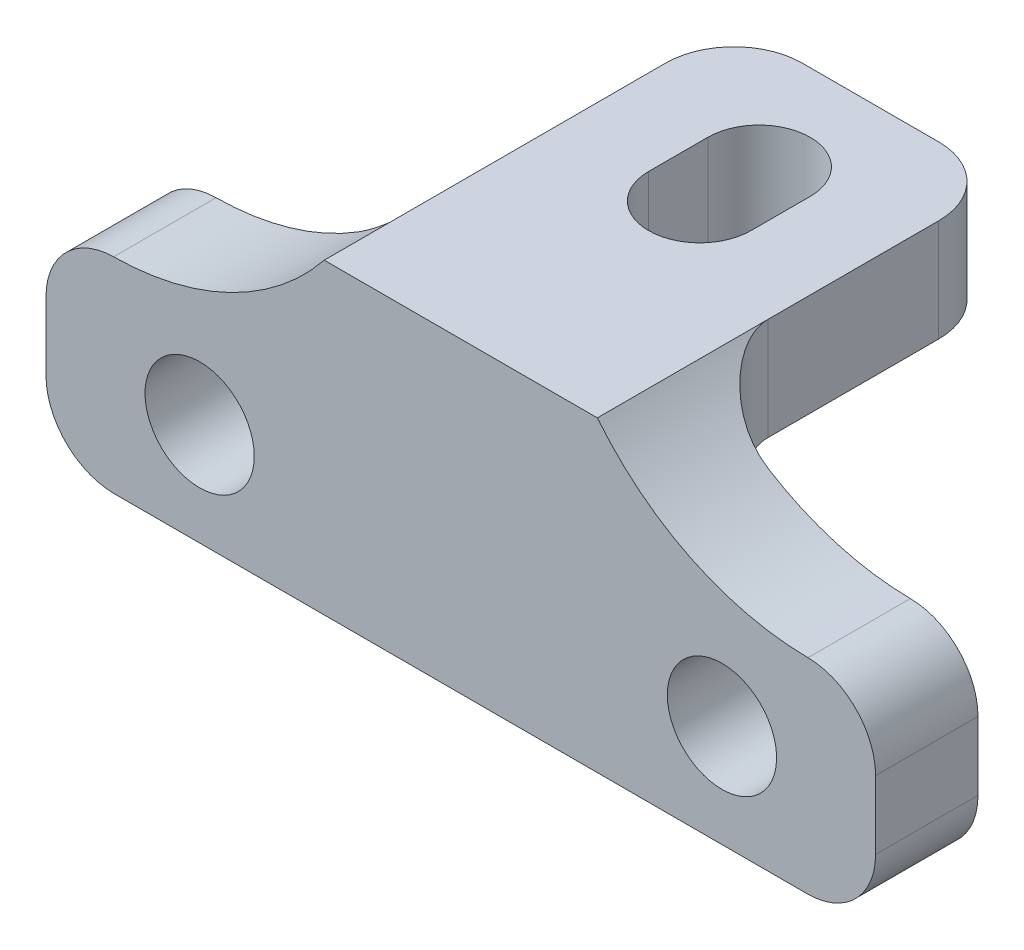
SolidWorks part; units mm, degrees
ref_plane "Plano frontal" through (0, 0, 0) normal (0, 0, 1) x (1, 0, 0)
ref_plane "Plano superior" through (0, 0, 0) normal (0, 1, 0) x (1, 0, 0)
ref_plane "Plano direito" through (0, 0, 0) normal (1, 0, 0) x (0, 0, -1)
sketch "Esboço1" plane through (0, 0, 0) normal (0, 0, 1) x (1, 0, 0)
  line L0 (-37.357, 24.6529) -> (-37.357, 18.6529) construction
  line L1 (-49.507, 24.6529) -> (-25.207, 24.6529)
  line L2 (-49.507, 24.6529) -> (-49.507, 18.6529)
  line L3 (-49.507, 18.6529) -> (-25.207, 18.6529)
  line L4 (-25.207, 24.6529) -> (-25.207, 18.6529)
  line L5 (-49.507, 21.6529) -> (-25.207, 21.6529) construction
  circle A0 centre (-45.007, 21.6529) radius 1.6
  circle A1 centre (-29.707, 21.6529) radius 1.6
  point P10 (0, 0)
  dimension "D3" = 15.3
  dimension "D1" = 24.3
  dimension "D2" = 6
base flange "Flange-base1" sketch "Esboço1" thickness 3 reverse thickness direction no parameters "D1"=0.7366
sketch "Esboço6" plane through (0, 24.6529, 0) normal (0, 1, 0) x (1, 0, 0)
  line L0 (-49.507, 0) -> (-25.207, 0) construction
  line L1 (-41.357, 0) -> (-33.357, 0)
  line L2 (-41.357, 0) -> (-41.357, 12)
  line L3 (-41.357, 12) -> (-33.357, 12)
  line L4 (-33.357, 0) -> (-33.357, 12)
  line L6 (-25.207, 0) -> (-49.507, 0) construction
  line L7 (-37.357, 3) -> (-37.357, 1.2859) construction
  line L8 (-25.207, 3) -> (-49.507, 3) construction
  line L9 (-37.357, 12) -> (-37.357, 3) construction
  line L10 (-37.357, 8.7354) -> (-37.357, 7) construction
  line L11 (-35.857, 8.7354) -> (-35.857, 7)
  line L12 (-38.857, 8.7354) -> (-38.857, 7)
  arc A0 (-35.857, 8.7354) -> (-38.857, 8.7354) centre (-37.357, 8.7354) ccw
  arc A1 (-38.857, 7) -> (-35.857, 7) centre (-37.357, 7) ccw
  point P15 (-37.357, 7.8677)
  point P20 (-37.357, 5.5)
  dimension "D4" = 2.5
  dimension "D1" = 4
  dimension "D2" = 4
  dimension "D3" = 12
extrude "Ressalto-extrusão1" add sketch "Esboço6" along normal blind 3
fillet "Filete1" radius 8 2 edges at (-33.357, 24.6529, -1.5) (-41.357, 24.6529, -1.5)
fillet "Filete2" radius 2 9 edges at (-33.357, 26.1529, -3) (-41.357, 26.1529, -3) (-41.357, 26.1529, -12) (-33.357, 26.1529, -12) (-25.207, 24.6529, -1.5) (-25.207, 18.6529, -1.5) (-49.507, 24.6529, -1.5) (-49.507, 18.6529, -1.5) (-37.357, 24.6529, -3)
sketch "Curva-Linhas1" [suppressed] plane through (0, 0, 0) normal (0, 1, 0) x (1, 0, 0)
sketch "Caixa delimitadora1" [suppressed] plane through (0, 0, 0) normal (0, 1, 0) x (1, 0, 0)
sheet metal parameters "Chapa metálica1" thickness 3 parameters "D1"=0.7366
flat pattern "Padrão-Plano1" [suppressed]
sketch "Curva-Linhas2" plane through (0, 0, 0) normal (0, 1, 0) x (1, 0, 0)
sketch3d "Caixa delimitadora2" [suppressed]
  line L0 (49.507, 18.6529, 0) -> (25.207, 18.6529, 0) construction
  line L1 (49.507, 24.6529, 0) -> (25.207, 24.6529, 0) construction
  line L2 (49.507, 18.6529, 0) -> (49.507, 24.6529, 0) construction
  line L3 (25.207, 18.6529, 0) -> (25.207, 24.6529, 0) construction
sheet metal parameters "Chapa metálica2" thickness 3 parameters "D1"=0.7366
flat pattern "Padrão-Plano1"
sketch "Curva-Linhas2" plane through (0, 0, 0) normal (0, 1, 0) x (1, 0, 0)
sketch3d "Caixa delimitadora2" [suppressed]
  line L0 (-49.507, 18.6529, 0) -> (-25.207, 18.6529, 0) construction
  line L1 (-49.507, 27.8372, 0) -> (-25.207, 27.8372, 0) construction
  line L2 (-49.507, 18.6529, 0) -> (-49.507, 27.8372, 0) construction
  line L3 (-25.207, 18.6529, 0) -> (-25.207, 27.8372, 0) construction
